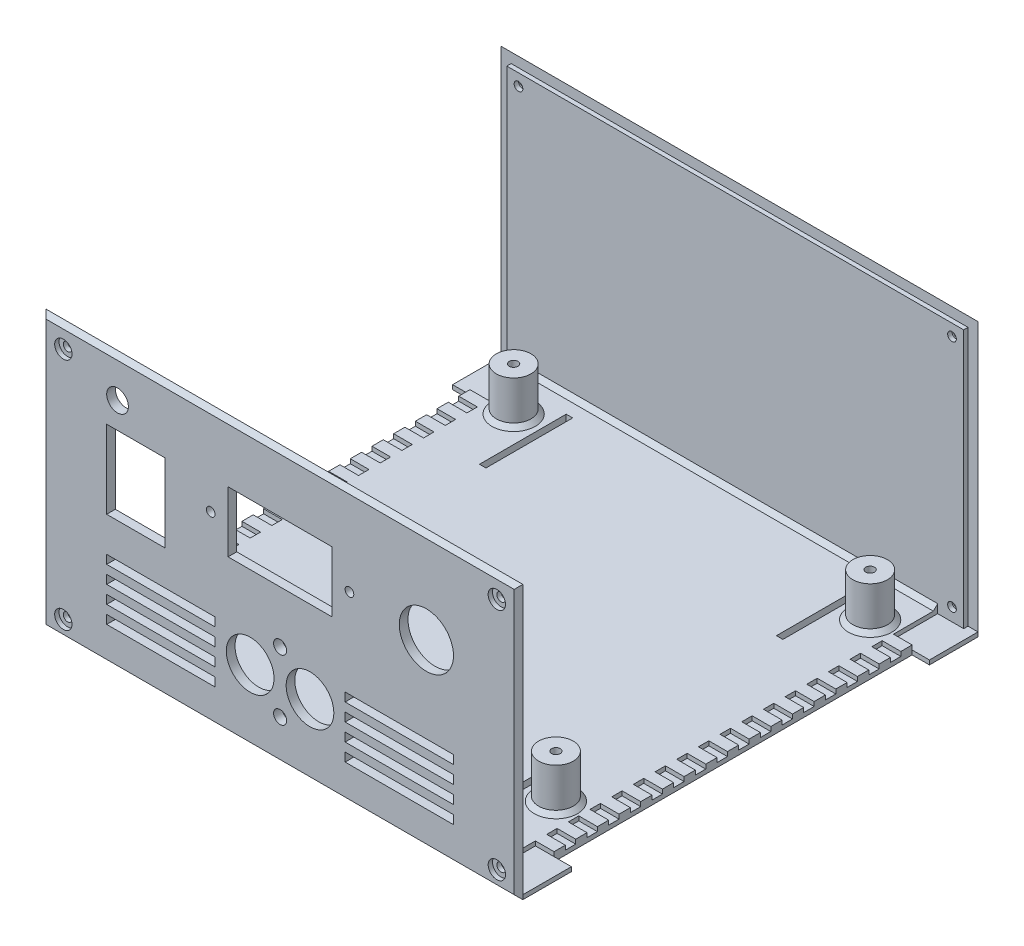
SolidWorks part; units mm, degrees
ref_plane "Front Plane" through (0, 0, 0) normal (0, 0, 1) x (1, 0, 0)
ref_plane "Top Plane" through (0, 0, 0) normal (0, 1, 0) x (1, 0, 0)
ref_plane "Right Plane" through (0, 0, 0) normal (1, 0, 0) x (0, 0, -1)
sketch "Sketch1" plane through (0, 0, 0) normal (0, 0, 1) x (1, 0, 0)
  line L1 (0, 0) -> (110, 0)
  line L2 (0, 0) -> (0, 64)
  line L3 (0, 64) -> (110, 64)
  line L4 (110, 0) -> (110, 64)
  dimension "D1" = 110
  dimension "D2" = 64
extrude "Boss-Extrude1" add sketch "Sketch1" against normal blind 94
sketch "Sketch2" plane through (110, 0, 0) normal (1, 0, 0) x (0, 0, -1)
  line L0 (94, 64) -> (0, 64) construction
  line L1 (2, 64) -> (92, 64)
  line L2 (2, 64) -> (2, 2)
  line L3 (2, 2) -> (92, 2)
  line L4 (92, 64) -> (92, 2)
  line L5 (0, 0) -> (0, 64) construction
  line L6 (94, 0) -> (0, 0) construction
  dimension "D1" = 90
  dimension "D2" = 2
  dimension "D3" = 2
extrude "Cut-Extrude1" cut sketch "Sketch2" against normal blind 110
sketch "Sketch3" plane through (0, 0, -2) normal (0, 0, -1) x (-1, 0, 0)
  line L0 (0, 2) -> (-110, 2) construction
  line L1 (-107.7, 61.7) -> (-2.3, 61.7)
  line L2 (-107.7, 61.7) -> (-107.7, 2)
  line L3 (-107.7, 2) -> (-2.3, 2)
  line L4 (-2.3, 61.7) -> (-2.3, 2)
  line L5 (-110, 64) -> (-110, 2) construction
  line L6 (0, 64) -> (-110, 64) construction
  line L7 (0, 64) -> (0, 2) construction
  line L9 (-110, 64) -> (0, 64)
  line L10 (-110, 64) -> (-110, 2)
  line L11 (-110, 2) -> (0, 2)
  line L12 (0, 64) -> (0, 2)
  line M6 (-110, 2) -> (0, 2)
  dimension "D1" = 2.3
  dimension "D2" = 2.3
  dimension "D3" = 2.3
sketch "Sketch4" plane through (0, 0, -92) normal (0, 0, 1) x (1, 0, 0)
  line L0 (0, 2) -> (110, 2) construction
  line L1 (2.3, 61.7) -> (107.7, 61.7)
  line L2 (2.3, 61.7) -> (2.3, 2)
  line L3 (2.3, 2) -> (107.7, 2)
  line L4 (107.7, 61.7) -> (107.7, 2)
  line L5 (0, 2) -> (0, 64) construction
  line L6 (0, 64) -> (110, 64) construction
  line L7 (110, 2) -> (110, 64) construction
  line L9 (0, 64) -> (110, 64)
  line L10 (0, 64) -> (0, 2)
  line L11 (0, 2) -> (110, 2)
  line L12 (110, 64) -> (110, 2)
  line M8 (0, 2) -> (110, 2)
  dimension "D1" = 2.3
  dimension "D2" = 2.3
  dimension "D3" = 2.3
extrude "Boss-Extrude2" add sketch "Sketch3" along normal blind 1 contours L4 L1 L2 M6 region at (55, 31.85, -2)
extrude "Boss-Extrude3" add sketch "Sketch4" along normal blind 1 contours L4 L1 L2 M8 region at (55, 31.85, -92)
sketch "Sketch5" plane through (0, 64, 0) normal (0, 1, 0) x (1, 0, 0)
  line L0 (0, 2) -> (0, 0) construction
  line L1 (0, 1) -> (110, 1)
  line L2 (0, 1) -> (0, 93)
  line L3 (0, 93) -> (110, 93)
  line L4 (110, 1) -> (110, 93)
  line L5 (110, 94) -> (110, 92) construction
  line L7 (0, 0) -> (110, 0)
  line L8 (0, 0) -> (0, 94)
  line L9 (0, 94) -> (110, 94)
  line L10 (110, 0) -> (110, 94)
  line M6 (0, 2) -> (0, 0)
  line M7 (0, 0) -> (110, 0)
  line M8 (110, 0) -> (110, 2)
extrude "Cut-Extrude6" cut sketch "Sketch5" against normal blind 101 contours L3 L10 L9 L8 | L1 M6 M7 M8 region at (55, 64, -0.5) region at (55, 64, -93.5)
sketch "Sketch6" plane through (0, 2, 0) normal (0, 1, 0) x (1, 0, 0)
  line L0 (0, 2) -> (0, 92) construction
  line L1 (0, 18.2) -> (110, 18.2)
  line L2 (0, 18.2) -> (0, 20.8)
  line L3 (0, 20.8) -> (110, 20.8)
  line L4 (110, 18.2) -> (110, 20.8)
  line L5 (110, 2) -> (110, 92) construction
  line L7 (0, 23.2) -> (110, 23.2)
  line L8 (0, 23.2) -> (0, 25.8)
  line L9 (0, 25.8) -> (110, 25.8)
  line L10 (110, 23.2) -> (110, 25.8)
  line L11 (0, 28.2) -> (110, 28.2)
  line L12 (0, 28.2) -> (0, 30.8)
  line L13 (0, 30.8) -> (110, 30.8)
  line L14 (110, 28.2) -> (110, 30.8)
  line L15 (0, 38.2) -> (110, 38.2)
  line L16 (0, 38.2) -> (0, 40.8)
  line L17 (0, 40.8) -> (110, 40.8)
  line L18 (110, 38.2) -> (110, 40.8)
  line L19 (0, 48.2) -> (110, 48.2)
  line L20 (0, 48.2) -> (0, 50.8)
  line L21 (0, 50.8) -> (110, 50.8)
  line L22 (110, 48.2) -> (110, 50.8)
  line L23 (0, 58.2) -> (110, 58.2)
  line L24 (0, 58.2) -> (0, 60.8)
  line L25 (0, 60.8) -> (110, 60.8)
  line L26 (110, 58.2) -> (110, 60.8)
  line L27 (0, 33.2) -> (110, 33.2)
  line L28 (0, 33.2) -> (0, 35.8)
  line L29 (0, 35.8) -> (110, 35.8)
  line L30 (110, 33.2) -> (110, 35.8)
  line L31 (0, 43.2) -> (110, 43.2)
  line L32 (0, 43.2) -> (0, 45.8)
  line L33 (0, 45.8) -> (110, 45.8)
  line L34 (110, 43.2) -> (110, 45.8)
  line L35 (0, 53.2) -> (110, 53.2)
  line L36 (0, 53.2) -> (0, 55.8)
  line L37 (0, 55.8) -> (110, 55.8)
  line L38 (110, 53.2) -> (110, 55.8)
  line L39 (0, 13.2) -> (110, 13.2)
  line L40 (0, 13.2) -> (0, 15.8)
  line L41 (0, 15.8) -> (110, 15.8)
  line L42 (110, 13.2) -> (110, 15.8)
  line L43 (0, 63.2) -> (110, 63.2)
  line L44 (0, 63.2) -> (0, 65.8)
  line L45 (0, 65.8) -> (110, 65.8)
  line L46 (110, 63.2) -> (110, 65.8)
  line L47 (0, 68.2) -> (110, 68.2)
  line L48 (0, 68.2) -> (0, 70.8)
  line L49 (0, 70.8) -> (110, 70.8)
  line L50 (110, 68.2) -> (110, 70.8)
  line L51 (0, 73.2) -> (110, 73.2)
  line L52 (0, 73.2) -> (0, 75.8)
  line L53 (0, 75.8) -> (110, 75.8)
  line L54 (110, 73.2) -> (110, 75.8)
  line L55 (0, 78.2) -> (110, 78.2)
  line L56 (0, 78.2) -> (0, 80.8)
  line L57 (0, 80.8) -> (110, 80.8)
  line L58 (110, 78.2) -> (110, 80.8)
  line L59 (107.7, 3) -> (2.3, 3) construction
  line L60 (2.3, 91) -> (107.7, 91) construction
  line L61 (101.7, 3) -> (8.3, 3)
  line L62 (101.7, 3) -> (101.7, 91)
  line L63 (101.7, 91) -> (8.3, 91)
  line L64 (8.3, 3) -> (8.3, 91)
  line L65 (106, 3) -> (106, 91)
  line L66 (4, 3) -> (4, 91)
  dimension "D1" = 2.6
  dimension "D2" = 2.6
  dimension "D3" = 2.6
  dimension "D4" = 2.6
  dimension "D5" = 2.6
  dimension "D6" = 2.6
  dimension "D7" = 2.6
  dimension "D8" = 2.6
  dimension "D9" = 2.6
  dimension "D10" = 2.6
  dimension "D11" = 2.6
  dimension "D12" = 2.6
  dimension "D13" = 2.6
  dimension "D14" = 2.6
  dimension "D15" = 2.4
  dimension "D16" = 2.4
  dimension "D17" = 2.4
  dimension "D18" = 2.4
  dimension "D19" = 2.4
  dimension "D20" = 2.4
  dimension "D21" = 2.4
  dimension "D22" = 2.4
  dimension "D23" = 2.4
  dimension "D24" = 2.4
  dimension "D25" = 2.4
  dimension "D26" = 2.4
  dimension "D27" = 2.4
  dimension "D28" = 10.2
  dimension "D29" = 8.3
  dimension "D30" = 8.3
  dimension "D31" = 4
  dimension "D32" = 4
extrude "Boss-Extrude4" add sketch "Sketch6" along normal blind 1 contours L39 L65 L41 L62 | L1 L65 L3 L62 | L7 L65 L9 L62 | L11 L65 L13 L62 | L27 L65 L29 L62 | L15 L65 L17 L62 | L31 L65 L33 L62 | L19 L65 L21 L62 | L35 L65 L37 L62 | L23 L65 L25 L62 | L55 L65 L57 L62 | L51 L65 L53 L62 | L47 L65 L49 L62 | L43 L65 L45 L62 | L66 L39 L64 L41 | L66 L1 L64 L3 | L66 L7 L64 L9 | L66 L11 L64 L13 | L66 L27 L64 L29 | L66 L15 L64 L17 | L66 L31 L64 L33 | L66 L19 L64 L21 | L66 L35 L64 L37 | L66 L23 L64 L25 | L66 L43 L64 L45 | L66 L47 L64 L49 | L66 L51 L64 L53 | L66 L55 L64 L57 | L62 L63 L64 L61 region at (6.15, 2, -19.5) region at (6.15, 2, -14.5) region at (103.85, 2, -19.5) region at (6.15, 2, -24.5) region at (103.85, 2, -14.5) region at (103.85, 2, -24.5) region at (6.15, 2, -29.5) region at (103.85, 2, -29.5) region at (6.15, 2, -34.5) region at (103.85, 2, -34.5) region at (6.15, 2, -39.5) region at (103.85, 2, -39.5) region at (6.15, 2, -44.5) region at (103.85, 2, -44.5) region at (6.15, 2, -49.5) region at (103.85, 2, -49.5) region at (6.15, 2, -54.5) region at (103.85, 2, -54.5) region at (6.15, 2, -59.5) region at (103.85, 2, -59.5) region at (6.15, 2, -64.5) region at (103.85, 2, -64.5) region at (6.15, 2, -69.5) region at (103.85, 2, -69.5) region at (6.15, 2, -74.5) region at (103.85, 2, -74.5) region at (6.15, 2, -79.5) region at (103.85, 2, -79.5)
sketch "Sketch7" plane through (0, 0, 0) normal (-1, 0, 0) x (0, 0, 1)
  line L0 (-93, 0) -> (-93, 64) construction
  line L1 (-93, 1) -> (-1, 1)
  line L2 (-93, 1) -> (-93, 0)
  line L3 (-93, 0) -> (-1, 0)
  line L4 (-1, 1) -> (-1, 0)
  dimension "D1" = 1
extrude "Cut-Extrude7" cut sketch "Sketch7" against normal blind 121
sketch "Sketch8" plane through (0, 2, 0) normal (0, 1, 0) x (1, 0, 0)
  line L0 (110, 2) -> (110, 92) construction
  line L1 (106, 13.2) -> (110, 13.2)
  line L2 (106, 13.2) -> (106, 80.8)
  line L3 (106, 80.8) -> (110, 80.8)
  line L4 (110, 13.2) -> (110, 80.8)
  line L5 (0, 2) -> (0, 92) construction
  line L6 (4, 13.2) -> (0, 13.2)
  line L7 (4, 13.2) -> (4, 80.8)
  line L8 (4, 80.8) -> (0, 80.8)
  line L9 (0, 13.2) -> (0, 80.8)
extrude "Cut-Extrude8" cut sketch "Sketch8" against normal blind 1
sketch "Sketch11" plane through (0, 0, -1) normal (0, 0, 1) x (1, 0, 0)
  line L0 (0, 64) -> (110, 64) construction
  line L1 (0, 1) -> (0, 64) construction
  line L2 (110, 1) -> (110, 64) construction
  line L3 (110, 1) -> (0, 1) construction
  circle A0 centre (5, 59) radius 2
  circle A1 centre (105, 59) radius 2
  circle A2 centre (105, 5) radius 2
  circle A3 centre (5, 5) radius 2
  dimension "D1" = 5
  dimension "D4" = 5
  dimension "D5" = 4
  dimension "D7" = 5
  dimension "D2" = 5
  dimension "D3" = 5
  dimension "4" = 5
  dimension "D8" = 4
sketch "Sketch13" plane through (0, 0, -1) normal (0, 0, 1) x (1, 0, 0)
  line L0 (0, 1) -> (0, 64) construction
  line L1 (0, 23) -> (110, 23)
  line L2 (0, 23) -> (0, 21)
  line L3 (0, 21) -> (110, 21)
  line L4 (110, 23) -> (110, 21)
  line L5 (110, 1) -> (110, 64) construction
  line L6 (110, 1) -> (0, 1) construction
  line L7 (0, 19) -> (110, 19)
  line L8 (0, 19) -> (0, 17)
  line L9 (0, 17) -> (110, 17)
  line L10 (110, 19) -> (110, 17)
  line L11 (0, 15) -> (110, 15)
  line L12 (0, 15) -> (0, 13)
  line L13 (0, 13) -> (110, 13)
  line L14 (110, 15) -> (110, 13)
  line L15 (0, 11) -> (110, 11)
  line L16 (0, 11) -> (0, 9)
  line L17 (0, 9) -> (110, 9)
  line L18 (110, 11) -> (110, 9)
  line L19 (0, 27) -> (110, 27)
  line L20 (0, 27) -> (0, 25)
  line L21 (0, 25) -> (110, 25)
  line L22 (110, 27) -> (110, 25)
  line L24 (15, 27) -> (40, 27)
  line L25 (15, 27) -> (15, 9)
  line L26 (15, 9) -> (40, 9)
  line L27 (40, 27) -> (40, 9)
  line L28 (70, 27) -> (95, 27)
  line L29 (70, 27) -> (70, 9)
  line L30 (70, 9) -> (95, 9)
  line L31 (95, 27) -> (95, 9)
  dimension "D1" = 2
  dimension "D2" = 2
  dimension "D3" = 2
  dimension "D4" = 2
  dimension "D5" = 2
  dimension "D6" = 2
  dimension "D7" = 2
  dimension "D8" = 2
  dimension "D9" = 2
  dimension "D10" = 8
  dimension "D11" = 25
  dimension "D12" = 15
  dimension "D13" = 15
  dimension "D14" = 25
extrude "Cut-Extrude13" cut sketch "Sketch13" against normal blind 2 contours L27 L1 L25 L3 | L27 L19 L25 L21 | L27 L7 L25 L9 | L27 L11 L25 L13 | L27 L15 L25 L17 | L31 L19 L29 L21 | L31 L1 L29 L3 | L31 L7 L29 L9 | L31 L11 L29 L13 | L31 L15 L29 L17 region at (27.5, 22, -1) region at (27.5, 26, -1) region at (82.5, 22, -1) region at (27.5, 18, -1) region at (82.5, 26, -1) region at (82.5, 18, -1) region at (27.5, 14, -1) region at (82.5, 14, -1) region at (27.5, 10, -1) region at (82.5, 10, -1)
sketch "Sketch14" plane through (0, 0, -1) normal (0, 0, 1) x (1, 0, 0)
  line L0 (48.1, 17.5002) -> (61.9, 17.5002)
  line L1 (15, 49) -> (28.5, 49)
  line L2 (15, 49) -> (15, 31)
  line L3 (15, 31) -> (28.5, 31)
  line L4 (28.5, 49) -> (28.5, 31)
  line L5 (0, 64) -> (110, 64) construction
  line L6 (15, 27) -> (15, 25) construction
  line L7 (15, 27) -> (40, 27) construction
  line L8 (95, 23) -> (95, 21) construction
  line L9 (15, 9) -> (40, 9) construction
  line L11 (55, 24.5005) -> (55, 10.5)
  line L12 (67, 43.5) -> (71, 43.5)
  line L13 (43, 50.5) -> (67, 50.5)
  line L14 (43, 50.5) -> (43, 36.5)
  line L15 (43, 36.5) -> (67, 36.5)
  line L16 (67, 50.5) -> (67, 36.5)
  line L17 (110, 1) -> (0, 1) construction
  line L18 (43, 43.5) -> (39, 43.5)
  circle A0 centre (88.75, 42.75) radius 6.25
  circle A1 centre (17.5, 55) radius 2.5
  circle A2 centre (48.1, 17.5002) radius 5.5
  circle A3 centre (61.9, 17.5002) radius 5.5
  circle A4 centre (55, 24.5005) radius 1.5
  circle A5 centre (55, 10.5) radius 1.5
  circle A6 centre (39, 43.5) radius 1
  circle A7 centre (71, 43.5) radius 1
  point P23 (55, 50.5)
  point P29 (55, 17.5002)
  point P30 (55, 17.5002)
  point P32 (55, 1)
  point P34 (55, 64)
  point P37 (95, 22)
  dimension "D1" = 13.5
  dimension "D3" = 13.8
  dimension "D4" = 14
  dimension "D12" = 0
  dimension "D2" = 18
  dimension "D5" = 0
  dimension "D6" = 4
  dimension "D7" = 2.5
  dimension "D8" = 6
  dimension "D9" = 24
  dimension "D10" = 0
  dimension "D11" = 0
  dimension "D13" = 0
  dimension "D14" = 14.0005
  dimension "D15" = 1.5
  dimension "D16" = 7.75
  dimension "D17" = 6.25
  dimension "D18" = 1.5
sketch "Sketch17" plane through (0, 0, -93) normal (0, 0, -1) x (-1, 0, 0)
  line L0 (-110, 1) -> (-110, 64) construction
  line L1 (-110, 3) -> (0, 3)
  line L2 (-110, 3) -> (-110, 1)
  line L3 (-110, 1) -> (0, 1)
  line L4 (0, 3) -> (0, 1)
  dimension "D1" = 2
extrude "Boss-Extrude5" add sketch "Sketch17" along normal blind 15
sketch "Sketch19" plane through (0, 3, 0) normal (0, 1, 0) x (1, 0, 0)
  line L0 (0, 108) -> (0, 93) construction
  line L1 (110, 108) -> (0, 108)
  line L2 (110, 108) -> (110, 106)
  line L3 (110, 106) -> (0, 106)
  line L4 (0, 108) -> (0, 106)
  dimension "D1" = 2
extrude "Boss-Extrude6" add sketch "Sketch19" along normal blind 61
sketch "Sketch20" plane through (0, 64, 0) normal (0, 1, 0) x (1, 0, 0)
  line L1 (0, 106) -> (2.3, 106)
  line L2 (0, 106) -> (0, 107)
  line L3 (0, 107) -> (2.3, 107)
  line L4 (2.3, 106) -> (2.3, 107)
  line L5 (110, 106) -> (107.7, 106)
  line L6 (110, 106) -> (110, 107)
  line L7 (110, 107) -> (107.7, 107)
  line L8 (107.7, 106) -> (107.7, 107)
  dimension "D1" = 2.3
  dimension "D2" = 2.3
extrude "Cut-Extrude15" cut sketch "Sketch20" against normal blind 62
sketch "Sketch21" plane through (0, 64, 0) normal (0, 1, 0) x (1, 0, 0)
  line L1 (107.7, 107) -> (2.3, 107)
  line L2 (107.7, 107) -> (107.7, 106)
  line L3 (107.7, 106) -> (2.3, 106)
  line L4 (2.3, 107) -> (2.3, 106)
extrude "Cut-Extrude16" cut sketch "Sketch21" against normal blind 2.3
sketch "Sketch22" plane through (0, 3, 0) normal (0, 1, 0) x (1, 0, 0)
  line L1 (0, 106) -> (8.3, 106)
  line L2 (0, 106) -> (0, 95.8)
  line L3 (0, 95.8) -> (8.3, 95.8)
  line L4 (8.3, 106) -> (8.3, 95.8)
  line L6 (110, 106) -> (101.7, 106)
  line L7 (110, 106) -> (110, 95.8)
  line L8 (110, 95.8) -> (101.7, 95.8)
  line L9 (101.7, 106) -> (101.7, 95.8)
  dimension "D1" = 10.2
  dimension "D2" = 8.3
  dimension "D3" = 10.2
  dimension "D4" = 8.3
extrude "Cut-Extrude17" cut sketch "Sketch22" against normal blind 1
sketch "Sketch24" plane through (0, 0, -108) normal (0, 0, -1) x (-1, 0, 0)
  line L1 (-105, 59) -> (-5, 59)
  line L2 (-105, 59) -> (-105, 5)
  line L3 (-105, 5) -> (-5, 5)
  line L4 (-5, 59) -> (-5, 5)
  line L5 (-110, 64) -> (0, 64) construction
  circle A0 centre (-105, 59) radius 2
  circle A1 centre (-5, 59) radius 2
  circle A2 centre (-105, 5) radius 2
  circle A3 centre (-5, 5) radius 2
  point P10 (-55, 64)
  point P11 (-55, 59)
  dimension "D3" = 0
  dimension "D1" = 54
  dimension "D2" = 100
  dimension "D4" = 5
extrude "Cut-Extrude18" cut sketch "Sketch24" against normal blind 1 contours A0 | A1 | A3 | A2
sketch "Sketch26" plane through (0, 3, 0) normal (0, 1, 0) x (1, 0, 0)
  line L0 (0, 95.8) -> (0, 93) construction
  line L1 (0, 93.2) -> (4, 93.2)
  line L2 (0, 93.2) -> (0, 80.8)
  line L3 (0, 80.8) -> (4, 80.8)
  line L4 (4, 93.2) -> (4, 80.8)
  line L5 (110, 95.8) -> (110, 93) construction
  line L6 (110, 93.2) -> (106, 93.2)
  line L7 (110, 93.2) -> (110, 80.8)
  line L8 (110, 80.8) -> (106, 80.8)
  line L9 (106, 93.2) -> (106, 80.8)
  dimension "D1" = 12.4
  dimension "D2" = 12.4
extrude "Cut-Extrude19" cut sketch "Sketch26" against normal blind 11 and the other way blind 71
sketch "Sketch27" plane through (0, 0, -91) normal (0, 0, 1) x (1, 0, 0)
  line L0 (10.1294, 3) -> (4, 3)
  line L1 (101.7, 3) -> (8.3, 3) construction
  line L2 (4, 61.7) -> (4, 2) construction
  line L4 (4, 3) -> (110, 3)
  line L5 (4, 3) -> (4, 64)
  line L6 (4, 64) -> (110, 64)
  line L7 (110, 3) -> (110, 64)
  line M5 (106, 61.7) -> (4, 61.7)
  line M6 (4, 61.7) -> (4, 2)
  line M9 (8.3, 3) -> (101.7, 3)
  line M12 (106, 2) -> (106, 61.7)
extrude "Cut-Extrude20" cut sketch "Sketch27" against normal blind 2 contours L4 L0 M9 M12 M5 M6 | L4 L7 L6 L5 M5 M12 region at (55, 32.35, -91) region at (107.223, 32.35, -91)
sketch "Sketch29" plane through (0, 3, 0) normal (0, 1, 0) x (1, 0, 0)
  line L1 (4, 93.2) -> (0, 93.2)
  line L2 (4, 93.2) -> (4, 95.8)
  line L3 (4, 95.8) -> (0, 95.8)
  line L4 (0, 93.2) -> (0, 95.8)
  line L5 (101.7, 91) -> (106, 91)
  line L6 (101.7, 91) -> (101.7, 93.2)
  line L7 (101.7, 93.2) -> (106, 93.2)
  line L8 (106, 91) -> (106, 93.2)
extrude "Cut-Extrude21" cut sketch "Sketch29" against normal blind 2
sketch "Sketch31" plane through (0, 3, 0) normal (0, 1, 0) x (1, 0, 0)
  line L0 (8.3, 80.8) -> (8.3, 91) construction
  line L1 (4, 91) -> (8.3, 91)
  line L2 (4, 91) -> (4, 83.2)
  line L3 (4, 83.2) -> (8.3, 83.2)
  line L4 (8.3, 91) -> (8.3, 83.2)
  line L5 (4, 80.8) -> (8.3, 80.8) construction
  line L6 (101.7, 80.8) -> (101.7, 93.2) construction
  line L7 (101.7, 90.8) -> (106, 90.8)
  line L8 (101.7, 90.8) -> (101.7, 83.2)
  line L9 (101.7, 83.2) -> (106, 83.2)
  line L10 (106, 90.8) -> (106, 83.2)
  line L11 (101.7, 80.8) -> (106, 80.8) construction
  line L12 (110, 93.2) -> (101.7, 93.2) construction
  dimension "D1" = 2.4
  dimension "D2" = 2.4
  dimension "D3" = 2.4
extrude "Boss-Extrude7" add sketch "Sketch31" against normal blind 1
sketch "Sketch32" plane through (0, 3, 0) normal (0, 1, 0) x (1, 0, 0)
  line L0 (101.7, 95.8) -> (110, 95.8) construction
  line L1 (110, 93.2) -> (106, 93.2)
  line L2 (110, 93.2) -> (110, 95.8)
  line L3 (110, 95.8) -> (106, 95.8)
  line L4 (106, 93.2) -> (106, 95.8)
extrude "Cut-Extrude22" cut sketch "Sketch32" against normal blind 11
sketch "Sketch33" plane through (0, 3, 0) normal (0, 1, 0) x (1, 0, 0)
  line L0 (4, 83.2) -> (4, 95.8) construction
  line L1 (4, 88.2) -> (106, 88.2)
  line L2 (4, 88.2) -> (4, 85.8)
  line L3 (4, 85.8) -> (106, 85.8)
  line L4 (106, 88.2) -> (106, 85.8)
  line L5 (106, 83.2) -> (106, 90.8) construction
  line L6 (101.7, 90.8) -> (101.7, 93.2)
  line L7 (101.7, 90.8) -> (3.9205, 90.8)
  line L8 (101.7, 93.2) -> (3.9205, 93.2)
  line L9 (3.9205, 90.8) -> (3.9205, 93.2)
  line L10 (8.3, 85.8) -> (8.3, 95.8)
  line L11 (101.7, 95.8) -> (101.7, 85.8)
  dimension "D1" = 2.4
  dimension "D2" = 2.6
extrude "Cut-Extrude24" cut sketch "Sketch33" against normal blind 1 contours L3 L10 L1 L2 | L7 L10 L8 L9 | L1 L11 L3 L4 region at (6.15, 3, -87) region at (103.85, 3, -87) region at (6.1103, 3, -92)
sketch "Sketch34" plane through (0, 2, 0) normal (0, 1, 0) x (1, 0, 0)
  line L0 (106, 91) -> (101.7, 91)
  line L1 (106, 91) -> (106, 93.1886)
  line L2 (101.7, 91) -> (101.7, 93.1886)
  line L3 (106, 93.1886) -> (101.7, 93.1886)
extrude "Boss-Extrude8" add sketch "Sketch34" against normal blind 1
sketch "Sketch35" plane through (0, 3, 0) normal (0, 1, 0) x (1, 0, 0)
  line L0 (13.8775, 96) -> (96.1225, 96)
  line L1 (13.8775, 96) -> (13.8775, 23.508)
  line L2 (13.8775, 23.508) -> (96.1225, 23.508)
  line L3 (96.1225, 96) -> (96.1225, 23.508)
  line L4 (8.3, 106) -> (101.7, 106) construction
  circle A0 centre (13.8775, 96) radius 4
  circle A1 centre (96.1225, 96) radius 4
  circle A2 centre (96.1225, 23.508) radius 4
  circle A3 centre (13.8775, 23.508) radius 4
  point P4 (55, 106)
  point P13 (55, 96)
  dimension "D1" = 72.492
  dimension "D2" = 82.245
  dimension "D3" = 10
  dimension "0" = 0
extrude "Boss-Extrude9" add sketch "Sketch35" along normal blind 10 contours A1 | A0 | A3 | A2
extrude "Cut-Extrude25" cut sketch "Sketch11" against normal blind 1
sketch "Sketch37" plane through (0, 13, 0) normal (0, 1, 0) x (1, 0, 0)
  circle A0 centre (96.1225, 23.508) radius 1
  circle A1 centre (13.8775, 23.508) radius 1
  circle A2 centre (96.1225, 96) radius 1
  circle A3 centre (13.8775, 96) radius 1
extrude "Cut-Extrude26" cut sketch "Sketch37" against normal blind 5
sketch "Sketch38" plane through (0, 1, 0) normal (0, -1, 0) x (1, 0, 0)
  line L0 (110, -108) -> (0, -108) construction
  line L1 (20, -102) -> (21.5, -102)
  line L2 (20, -102) -> (20, -7)
  line L3 (20, -7) -> (21.5, -7)
  line L4 (21.5, -102) -> (21.5, -7)
  line L5 (88.5, -102) -> (90, -102)
  line L6 (88.5, -102) -> (88.5, -7)
  line L7 (88.5, -7) -> (90, -7)
  line L8 (90, -102) -> (90, -7)
  line L9 (110, -1) -> (0, -1) construction
  line L10 (0, -95.8) -> (0, -108) construction
  line L11 (110, -108) -> (110, -95.8) construction
  line L13 (20, -82) -> (90, -82)
  line L14 (20, -82) -> (20, -27)
  line L15 (20, -27) -> (90, -27)
  line L16 (90, -82) -> (90, -27)
  dimension "D1" = 1.5
  dimension "D2" = 1.5
  dimension "D3" = 0
  dimension "D4" = 6
  dimension "D5" = 0
  dimension "D6" = 6
  dimension "D7" = 20
  dimension "D8" = 20
  dimension "D9" = 20
  dimension "D10" = 20
extrude "Cut-Extrude27" cut sketch "Sketch38" against normal blind 5 contours L13 L2 L1 L4 | L2 L15 L4 L3 | L6 L15 L8 L7 | L13 L6 L5 L8 region at (20.75, 1, -92) region at (20.75, 1, -17) region at (89.25, 1, -92) region at (89.25, 1, -17)
sketch "Sketch39" plane through (0, 0, -2) normal (0, 0, 1) x (1, 0, 0)
  circle A0 centre (105, 5) radius 1
  circle A1 centre (105, 59) radius 1
  circle A2 centre (5, 5) radius 1
  circle A3 centre (5, 59) radius 1
extrude "Cut-Extrude28" cut sketch "Sketch39" against normal blind 145
chamfer "Chamfer1" distance 1 angle 45 8 edges at (55, 1, -108) (55, 1, -1) (13.8775, 3, -92) (13.8775, 3, -19.508) (96.1225, 3, -19.508) (96.1225, 3, -92) (55, 3, -3) (55, 3, -106)
chamfer "Chamfer2" distance 1 angle 45 6 edges at (0, 33, -108) (55, 64, -108) (110, 33, -108) (110, 33, -1) (55, 64, -1) (0, 33, -1)
sketch "Sketch41" plane through (0, 0, -1) normal (0, 0, 1) x (1, 0, 0)
  line L1 (15, 27) -> (40, 27)
  line L2 (15, 27) -> (15, 25)
  line L3 (15, 25) -> (40, 25)
  line L4 (40, 27) -> (40, 25)
  line L5 (70, 27) -> (95, 27)
  line L6 (70, 27) -> (70, 25)
  line L7 (70, 25) -> (95, 25)
  line L8 (95, 27) -> (95, 25)
extrude "Boss-Extrude10" add sketch "Sketch41" against normal blind 2
extrude "Cut-Extrude29" cut sketch "Sketch14" against normal blind 2 contours A1 | L1 L4 L3 L2 | L14 L15 L16 L13 | A6 | A7 | A0 | A2 | A3 | A4 | A5
sketch "Sketch42" plane through (0, 0, -108) normal (0, 0, -1) x (-1, 0, 0)
  text T0 "G1" font "ROG Fonts" height in points 60
extrude "Cut-Extrude30" cut sketch "Sketch42" against normal blind 1
sketch "Sketch43" plane through (0, 1, 0) normal (0, -1, 0) x (1, 0, 0)
  line L0 (106, -93.1886) -> (106, -13.2) construction
  line L1 (106, -92.7016) -> (101.5369, -92.7016)
  line L2 (106, -92.7016) -> (106, -93.6681)
  line L3 (106, -93.6681) -> (101.5369, -93.6681)
  line L4 (101.5369, -92.7016) -> (101.5369, -93.6681)
extrude "Boss-Extrude11" add sketch "Sketch43" against normal blind 1
